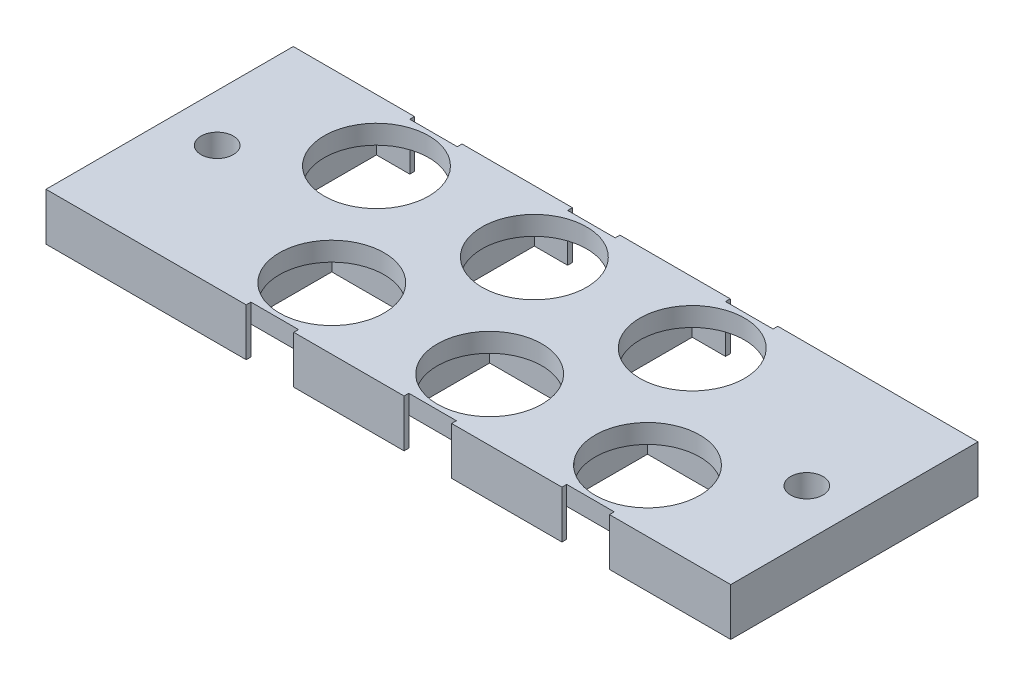
SolidWorks part; units mm, degrees
ref_plane "Front Plane" through (0, 0, 0) normal (0, 0, 1) x (1, 0, 0)
ref_plane "Top Plane" through (0, 0, 0) normal (0, 1, 0) x (1, 0, 0)
ref_plane "Right Plane" through (0, 0, 0) normal (1, 0, 0) x (0, 0, -1)
sketch "Sketch1" plane through (0, 0, 0) normal (0, 1, 0) x (1, 0, 0)
  line L0 (5.3864, -4.1649) -> (1.7864, -4.1649)
  line L1 (18.3864, -4.1649) -> (21.9864, -4.1649)
  line L2 (30.2864, -30.1649) -> (26.6864, -30.1649)
  line L3 (13.6864, -30.1649) -> (10.0864, -30.1649)
  line L4 (43.2864, -30.1649) -> (52.0364, -30.1649)
  line L5 (52.0364, -30.1649) -> (52.0364, -4.1649)
  line L6 (52.0364, -4.1649) -> (34.9864, -4.1649)
  line L7 (-11.2136, -4.1649) -> (-19.9636, -4.1649)
  line L8 (-19.9636, -4.1649) -> (-19.9636, -30.1649)
  line L9 (-19.9636, -30.1649) -> (-2.9136, -30.1649)
  line L10 (-14.9636, -4.1649) -> (-14.9636, -30.1649) construction
  line L11 (47.0364, -4.1649) -> (47.0364, -30.1649) construction
  circle A0 centre (-14.9636, -17.1649) radius 1.7
  circle A1 centre (47.0364, -17.1649) radius 1.7
  line B0 (34.9864, -17.1649) -> (34.9864, -4.1649)
  line B1 (10.0864, -30.1649) -> (6.0864, -30.1649)
  line B2 (-2.4136, -29.6649) -> (9.5864, -29.6649)
  line B3 (10.0864, -30.1649) -> (10.0864, -17.1649)
  line B4 (26.6864, -30.1649) -> (26.6864, -17.1649)
  line B5 (43.2864, -30.1649) -> (43.2864, -17.1649)
  line B6 (-2.9136, -17.1649) -> (-2.9136, -30.1649)
  line B7 (9.5864, -29.6649) -> (9.5864, -17.6649)
  line B8 (30.2864, -17.1649) -> (30.2864, -30.1649)
  line B9 (21.9864, -4.1649) -> (21.9864, -17.1649)
  line B10 (34.4864, -16.6649) -> (34.4864, -4.6649)
  line B11 (17.8864, -16.6649) -> (17.8864, -4.6649)
  line B12 (1.7864, -17.1649) -> (1.7864, -4.1649)
  line B13 (42.7864, -29.6649) -> (42.7864, -17.6649)
  line B14 (14.1864, -29.6649) -> (26.1864, -29.6649)
  line B15 (30.7864, -17.6649) -> (30.7864, -29.6649)
  line B16 (30.7864, -17.6649) -> (42.7864, -29.6649) construction
  line B17 (14.1864, -17.6649) -> (26.1864, -29.6649) construction
  line B18 (-2.4136, -17.6649) -> (9.5864, -29.6649) construction
  line B19 (43.2864, -17.1649) -> (30.2864, -17.1649)
  line B20 (1.2864, -16.6649) -> (1.2864, -4.6649)
  line B21 (14.1864, -17.6649) -> (14.1864, -29.6649)
  line B22 (26.6864, -30.1649) -> (22.6864, -30.1649)
  line B23 (30.2864, -30.1649) -> (34.2864, -30.1649)
  line B24 (43.2864, -30.1649) -> (39.2864, -30.1649)
  line B25 (-10.7136, -10.6649) -> (1.2864, -10.6649) construction
  line B26 (5.8864, -10.6649) -> (17.8864, -10.6649) construction
  line B27 (22.4864, -10.6649) -> (34.4864, -10.6649) construction
  line B28 (-2.4136, -23.6649) -> (9.5864, -23.6649) construction
  line B29 (14.1864, -23.6649) -> (26.1864, -23.6649) construction
  line B30 (30.7864, -23.6649) -> (42.7864, -23.6649) construction
  line B31 (-27.9152, -23.6649) -> (50.7342, -23.6649) construction
  line B32 (21.9864, -17.1649) -> (34.9864, -17.1649)
  line B33 (-27.9152, -10.6649) -> (50.7342, -10.6649) construction
  line B34 (28.4864, -16.6649) -> (28.4864, -4.6649) construction
  line B35 (36.7864, -17.6649) -> (36.7864, -29.6649) construction
  line B36 (20.1864, -17.6649) -> (20.1864, -29.6649) construction
  line B37 (11.8864, -16.6649) -> (11.8864, -4.6649) construction
  line B38 (3.5864, -17.6649) -> (3.5864, -29.6649) construction
  line B39 (-4.7136, -16.6649) -> (-4.7136, -4.6649) construction
  line B40 (22.4864, -4.6649) -> (22.4864, -16.6649)
  line B41 (22.4864, -16.6649) -> (34.4864, -16.6649)
  line B42 (34.4864, -4.6649) -> (22.4864, -4.6649)
  line B43 (34.4864, -16.6649) -> (22.4864, -4.6649) construction
  line B44 (34.4864, -4.6649) -> (22.4864, -16.6649) construction
  line B45 (34.9864, -4.1649) -> (30.9864, -4.1649)
  line B46 (21.9864, -4.1649) -> (25.9864, -4.1649)
  line B47 (30.9864, -4.1649) -> (30.9864, -4.6649)
  line B48 (25.9864, -4.1649) -> (25.9864, -4.6649)
  circle B49 centre (28.4864, -10.6649) radius 5.5
  line B50 (-2.4136, -17.6649) -> (-2.4136, -29.6649)
  line B51 (9.5864, -17.6649) -> (-2.4136, -17.6649)
  line B52 (-2.4136, -29.6649) -> (9.5864, -17.6649) construction
  line B53 (10.0864, -17.1649) -> (-2.9136, -17.1649)
  line B54 (-2.9136, -30.1649) -> (1.0864, -30.1649)
  line B55 (1.0864, -30.1649) -> (1.0864, -29.6649)
  line B56 (6.0864, -30.1649) -> (6.0864, -29.6649)
  circle B57 centre (3.5864, -23.6649) radius 5.5
  line B58 (26.1864, -29.6649) -> (26.1864, -17.6649)
  line B59 (26.1864, -17.6649) -> (14.1864, -17.6649)
  line B60 (14.1864, -29.6649) -> (26.1864, -17.6649) construction
  line B61 (26.6864, -17.1649) -> (13.6864, -17.1649)
  line B62 (13.6864, -17.1649) -> (13.6864, -30.1649)
  line B63 (13.6864, -30.1649) -> (17.6864, -30.1649)
  line B64 (17.6864, -30.1649) -> (17.6864, -29.6649)
  line B65 (22.6864, -30.1649) -> (22.6864, -29.6649)
  circle B66 centre (20.1864, -23.6649) radius 5.5
  line B67 (42.7864, -17.6649) -> (30.7864, -17.6649)
  line B68 (30.7864, -29.6649) -> (42.7864, -29.6649)
  line B69 (30.7864, -29.6649) -> (42.7864, -17.6649) construction
  line B70 (34.2864, -30.1649) -> (34.2864, -29.6649)
  line B71 (39.2864, -30.1649) -> (39.2864, -29.6649)
  circle B72 centre (36.7864, -23.6649) radius 5.5
  line B73 (5.8864, -4.6649) -> (5.8864, -16.6649)
  line B74 (5.8864, -16.6649) -> (17.8864, -16.6649)
  line B75 (17.8864, -4.6649) -> (5.8864, -4.6649)
  line B76 (17.8864, -16.6649) -> (5.8864, -4.6649) construction
  line B77 (17.8864, -4.6649) -> (5.8864, -16.6649) construction
  line B78 (5.3864, -17.1649) -> (18.3864, -17.1649)
  line B79 (18.3864, -17.1649) -> (18.3864, -4.1649)
  line B80 (5.3864, -4.1649) -> (5.3864, -17.1649)
  line B81 (18.3864, -4.1649) -> (14.3864, -4.1649)
  line B82 (5.3864, -4.1649) -> (9.3864, -4.1649)
  line B83 (14.3864, -4.1649) -> (14.3864, -4.6649)
  line B84 (9.3864, -4.1649) -> (9.3864, -4.6649)
  circle B85 centre (11.8864, -10.6649) radius 5.5
  line B86 (-10.7136, -4.6649) -> (-10.7136, -16.6649)
  line B87 (-10.7136, -16.6649) -> (1.2864, -16.6649)
  line B88 (1.2864, -4.6649) -> (-10.7136, -4.6649)
  line B89 (1.2864, -16.6649) -> (-10.7136, -4.6649) construction
  line B90 (1.2864, -4.6649) -> (-10.7136, -16.6649) construction
  line B91 (-11.2136, -17.1649) -> (1.7864, -17.1649)
  line B92 (-11.2136, -4.1649) -> (-11.2136, -17.1649)
  line B93 (1.7864, -4.1649) -> (-2.2136, -4.1649)
  line B94 (-11.2136, -4.1649) -> (-7.2136, -4.1649)
  line B95 (-2.2136, -4.1649) -> (-2.2136, -4.6649)
  line B96 (-7.2136, -4.1649) -> (-7.2136, -4.6649)
  circle B97 centre (-4.7136, -10.6649) radius 5.5
  dimension "D1" = 8.75
  dimension "D2" = 8.75
  dimension "D3" = 5
  dimension "D4" = 5
sketch_block_instance "Block1-5"
sketch_block "Block1" parameters "D3"=6, "D1"=12, "D2"=12, "D4"=12, "D5"=78.6494, "D6"=78.6494, "D7"=78.6494, "D8"=10.3235, "D9"=14.0261, "D10"=17.7654, "D11"=23.7534, "D12"=22.7743, "D13"=54.5
sketch_block_instance "Block2-2"
sketch_block "Block2" parameters "D2"=8, "D1"=12
sketch_block_instance "Block2-3"
sketch_block_instance "Block2-4"
sketch_block_instance "Block2-5"
sketch_block_instance "Block2-6"
sketch_block_instance "Block2-7"
sketch_block_instance "Block3-1"
sketch_block "Block3"
sketch_block_instance "Block4-1"
sketch_block "Block4"
sketch_block_instance "Block5-1"
sketch_block "Block5"
sketch_block_instance "Block6-1"
sketch_block "Block6"
sketch_block_instance "Block7-1"
sketch_block "Block7"
sketch_block_instance "Block8-1"
sketch_block "Block8"
extrude "Boss-Extrude1" add sketch "Sketch1" against normal blind 2 contours B50 B2 B7 B51 B57 | B20 B88 B86 B87 B97 | B11 B75 B73 B74 B85 | B21 B14 B58 B59 B66 | B10 B42 B40 B41 B49 | B15 B68 B13 B67 B72 region at (11.8864, 0, 4.8346) region at (-0.4636, 0, 4.8346) region at (3.5864, 0, 29.4952) region at (15.9364, 0, 29.4952) region at (28.4864, 0, 4.8346) region at (32.5364, 0, 29.4952)
extrude "Boss-Extrude2" add sketch "Sketch1<3>" against normal blind 5 contours B92 L7 L8 L9 B6 B91 A0 | B5 L4 L5 L6 B0 B19 A1 | B78 B3 L3 B62 | B8 B32 B4 L2 | B12 B53 B80 L0 | B79 B61 B9 L1 | B56 B1 B3 B53 B6 B54 B55 B2 B50 B51 B7 | B65 B22 B4 B32 B61 B62 B63 B64 B14 B21 B59 B58 | B71 B24 B5 B19 B32 B8 B23 B70 B68 B15 B67 B13 | B48 B46 B9 B32 B0 B45 B47 B42 B10 B41 B40 | B84 B82 B80 B53 B78 B61 B79 B81 B83 B75 B11 B74 B73 | B96 B94 B92 B91 B53 B12 B93 B95 B88 B20 B87 B86 region at (3.5864, 0, 10.6649) region at (7.3864, 0, 4.3487) region at (1.6025, 0, 10.6649) region at (7.7364, 0, 17.3487) region at (11.8864, 0, 23.6649) region at (-12.7872, 0, 19.3141) region at (16.0364, 0, 17.3487) region at (20.1864, 0, 10.6649) region at (22.1702, 0, 10.6649) region at (28.4864, 0, 23.6649) region at (32.6364, 0, 17.3487) region at (44.8599, 0, 15.0156)
sketch "Sketch1<3>" plane through (0, 0, 0) normal (0, 1, 0) x (1, 0, 0) same geometry as "Sketch1"
sketch "Sketch2" plane through (0, -5, 0) normal (0, -1, 0) x (-1, 0, 0)
  text T0 "F8"
extrude "Cut-Extrude1" cut sketch "Sketch2" against normal blind 1
